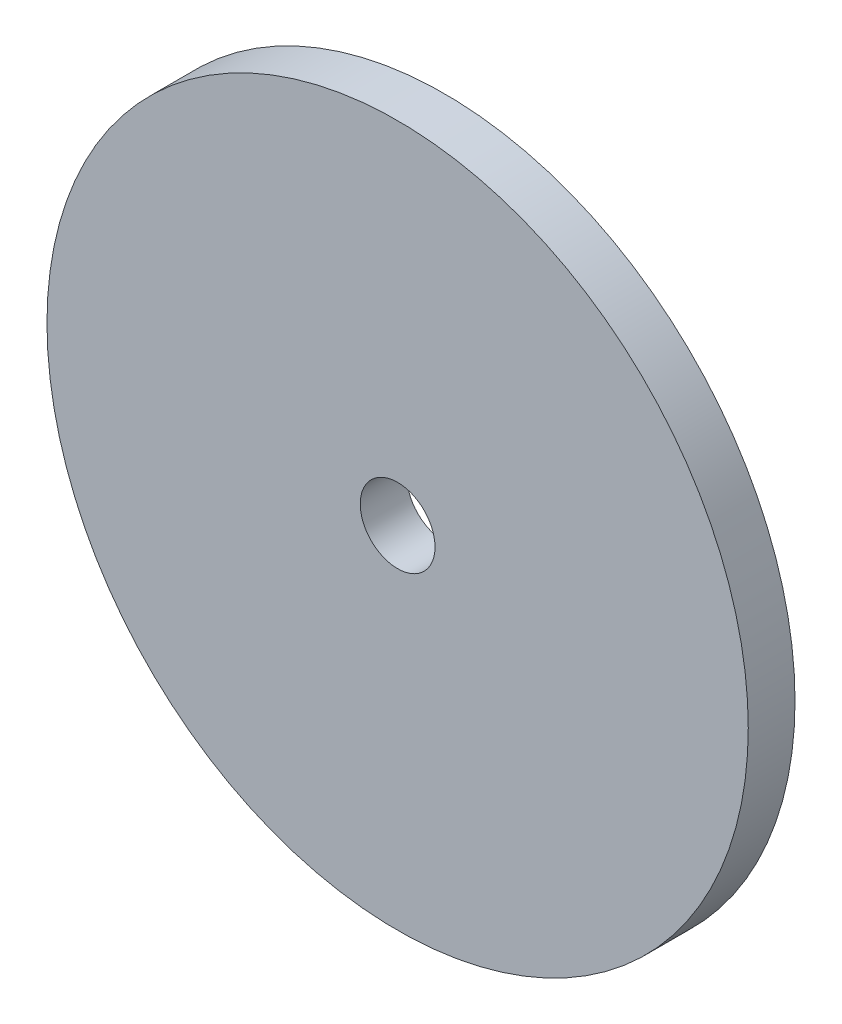
SolidWorks part; units mm, degrees
ref_plane "Front Plane" through (0, 0, 0) normal (0, 0, 1) x (1, 0, 0)
ref_plane "Top Plane" through (0, 0, 0) normal (0, 1, 0) x (1, 0, 0)
ref_plane "Right Plane" through (0, 0, 0) normal (1, 0, 0) x (0, 0, -1)
sketch "Sketch1" plane through (0, 0, 0) normal (0, 0, 1) x (1, 0, 0)
  circle A2 centre (0, 0) radius 8 construction
  circle A3 centre (0, 0) radius 8
  circle A4 centre (0, 0) radius 75 construction
  circle A5 centre (0, 0) radius 75
extrude "Boss-Extrude1" add sketch "Sketch1" along normal blind 10
